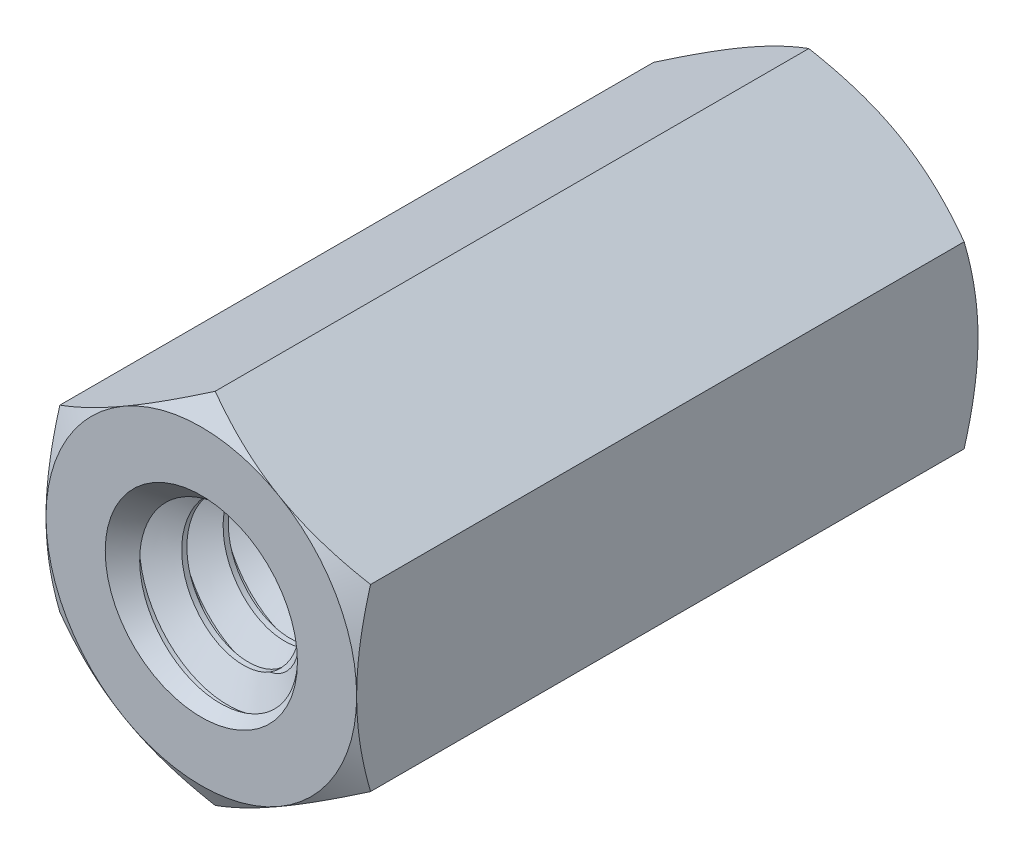
SolidWorks part; units mm, degrees
ref_plane "Front Plane" through (0, 0, 0) normal (0, 0, 1) x (1, 0, 0)
ref_plane "Top Plane" through (0, 0, 0) normal (0, 1, 0) x (1, 0, 0)
ref_plane "Right Plane" through (0, 0, 0) normal (1, 0, 0) x (0, 0, -1)
sketch "Sketch3" plane through (0, 0, 0) normal (1, 0, 0) x (0, 0, -1)
  line L0 (-4.7625, 0) -> (4.7625, 0) construction
  line L1 (0, 2.3813) -> (0, -2.3813) construction
  line L2 (-4.7625, 1.4224) -> (-4.7625, -1.4224) construction
  point P2 (0, 0)
  point P3 (0, 0)
  dimension "D1" = 4.7625
  dimension "Length" = 9.525
  dimension "Min Thread Length" = 4.7625
  dimension "Thread Dia" = 2.8448
  dimension "Hex" = 4.7625
sketch "Sketch1" plane through (0, 0, 0) normal (0, 0, 1) x (1, 0, 0)
  line L1 (0, 2.7496) -> (-2.3813, 1.3748)
  line L2 (-2.3813, 1.3748) -> (-2.3813, -1.3748)
  line L3 (-2.3813, -1.3748) -> (0, -2.7496)
  line L4 (0, -2.7496) -> (2.3813, -1.3748)
  line L5 (2.3813, -1.3748) -> (2.3813, 1.3748)
  line L6 (2.3813, 1.3748) -> (0, 2.7496)
  circle A0 centre (0, 0) radius 2.3813 construction
  circle A1 centre (0, 0) radius 1.4224
extrude "Extrude1" add sketch "Sketch1" along normal up to vertex (4.7625 mm away) and the other way up to vertex (4.7625 mm away) up to point (0, 0, 4.7625) other way up to point (0, 0, -4.7625)
sketch "Sketch11" plane through (0, 0, -4.7625) normal (0, 0, -1) x (-1, 0, 0)
  circle A0 centre (0, 0) radius 1.4224 construction
  circle A1 centre (0, 0) radius 1.4224
curve "Helix/Spiral1" pitch 0.635 height 10.16 radius 1.4224 centre (0, 0, -4.7625) axis (0, 0, 1) start towards (0, 1, 0) parameters "Pitch"=0.635
sketch "Sketch12" plane through (0, 0, 0) normal (1, 0, 0) x (0, 0, -1)
  line L0 (5.3181, 1.4224) -> (4.7625, 1.4224)
  line L1 (5.3181, 1.4224) -> (5.08, 1.01)
  line L2 (5.08, 1.01) -> (5.0006, 1.01)
  line L3 (5.0006, 1.01) -> (4.7625, 1.4224)
  line L4 (5.0403, 1.01) -> (5.0403, 1.4224) construction
  line L5 (5.1991, 1.2162) -> (4.8816, 1.2162) construction
  dimension "D1" = 0.0794
  dimension "D2" = 0.3175
  dimension "D3" = 60
sweep "Sweep1" add profiles "Sketch12" path "Helix/Spiral1"
sketch "Sketch6" plane through (0, 0, -4.7625) normal (0, 0, -1) x (-1, 0, 0)
  line L6 (0, 2.7496) -> (-2.3813, 1.3748)
  line L7 (-2.3813, 1.3748) -> (-2.3813, -1.3748)
  line L8 (-2.3813, -1.3748) -> (0, -2.7496)
  line L9 (0, -2.7496) -> (2.3813, -1.3748)
  line L10 (2.3813, -1.3748) -> (2.3813, 1.3748)
  line L11 (2.3813, 1.3748) -> (0, 2.7496)
  line L12 (0, 2.7496) -> (-2.3813, 1.3748)
  line L13 (-2.3813, 1.3748) -> (-2.3813, -1.3748)
  line L14 (-2.3813, -1.3748) -> (0, -2.7496)
  line L15 (0, -2.7496) -> (2.3813, -1.3748)
  line L16 (2.3813, -1.3748) -> (2.3813, 1.3748)
  line L17 (2.3813, 1.3748) -> (0, 2.7496)
  dimension "D1" = 0
extrude "Extrude2" cut sketch "Sketch6" along normal through all
sketch "Sketch7" plane through (0, 0, -4.7625) normal (0, 0, -1) x (-1, 0, 0)
  circle A2 centre (0, 0) radius 1.4732
  circle A3 centre (0, 0) radius 1.4732
  dimension "D1" = 0.0508
extrude "Extrude3" cut sketch "Sketch7" against normal through all draft 43
sketch "Sketch8" plane through (0, 0, -4.7625) normal (0, 0, -1) x (-1, 0, 0)
  circle A0 centre (0, 0) radius 2.3813 construction
  circle A1 centre (0, 0) radius 2.3813
extrude "Extrude4" cut sketch "Sketch8" against normal through all draft 60 flip side to cut
mirror "Mirror1" about plane through (0, 0, 0) normal (0, 0, 1) of "Extrude2", "Extrude3", "Extrude4"
sketch "Sketch9" [suppressed] plane through (0, 0, 0) normal (1, 0, 0) x (0, 0, -1)
  line L1 (-1.5875, 0.8128) -> (1.5875, 0.8128)
  line L2 (-1.5875, 0.8128) -> (-1.5875, 0)
  line L3 (-1.5875, 0) -> (1.5875, 0)
  line L4 (1.5875, 0.8128) -> (1.5875, 0)
  line L7 (-6.35, 0) -> (6.35, 0) construction
revolve "Revolve" [suppressed] add sketch "Sketch9" angle 360 about L0
sketch "Sketch10" [suppressed] plane through (0, 0, 0) normal (1, 0, 0) x (0, 0, -1)
  line L0 (6.35, 0.762) -> (1.5875, 0.762)
  line L1 (-6.35, 0.762) -> (-1.5875, 0.762)
  line L2 (1.5875, 0.762) -> (1.5875, -0.762)
  line L3 (-6.35, -0.8128) -> (-1.5875, -0.8128)
  line L4 (-1.5875, 0.762) -> (-1.5875, -0.8128)
  line L5 (1.5875, -0.762) -> (6.35, -0.762)
equation "\"D1@Sketch3\" = \"Min Thread Length@Sketch3\""
equation "\"D3@Helix/Spiral1\" = \"Length@Sketch3\"+\"Pitch@Helix/Spiral1\""
equation "\"D1@Sketch12\" = \"Pitch@Helix/Spiral1\"*.125"
equation "\"D2@Sketch12\" = \"Pitch@Helix/Spiral1\"*.5"
